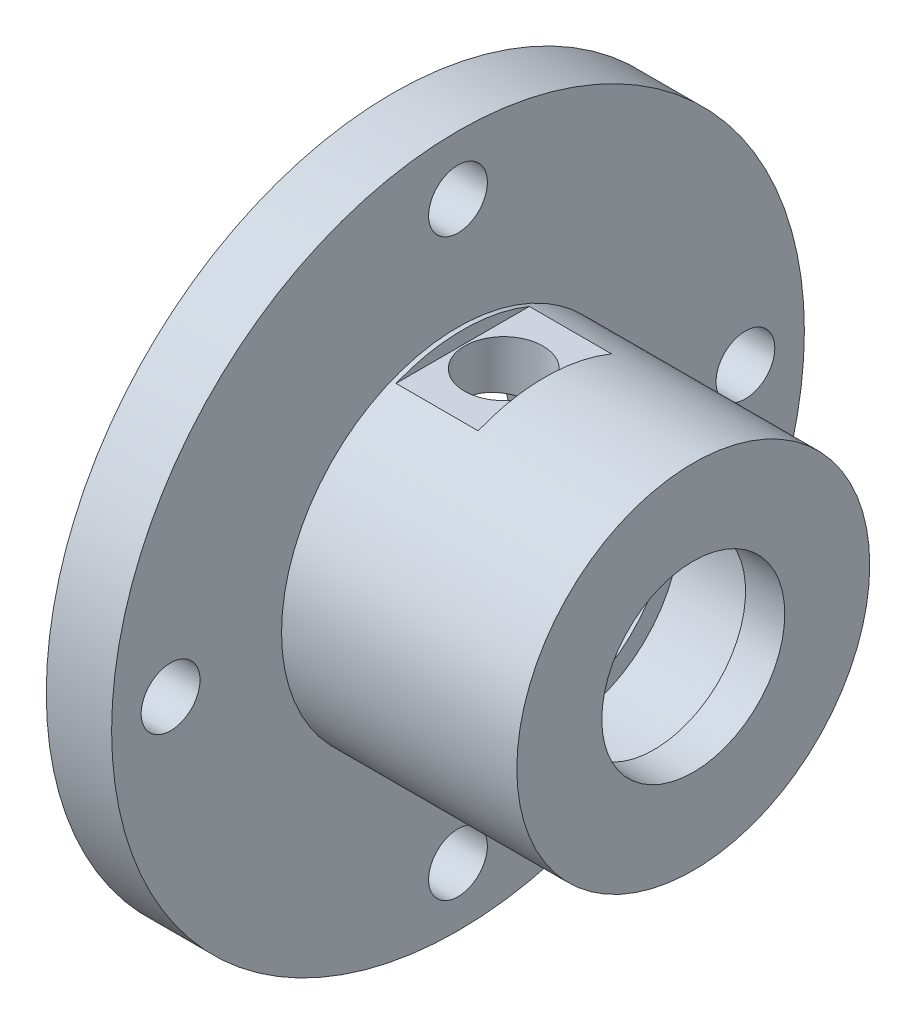
SolidWorks part; units mm, degrees
ref_plane "Front Plane" through (0, 0, 0) normal (0, 0, 1) x (1, 0, 0)
ref_plane "Top Plane" through (0, 0, 0) normal (0, 1, 0) x (1, 0, 0)
ref_plane "Right Plane" through (0, 0, 0) normal (1, 0, 0) x (0, 0, -1)
sketch "Sketch1" plane through (0, 0, 0) normal (1, 0, 0) x (0, 0, -1)
  circle A0 centre (0, 0) radius 26.5
  circle A2 centre (0, -21.9877) radius 2.25
  circle A3 centre (-21.9877, 0) radius 2.25
  circle A4 centre (0, 21.9877) radius 2.25
  circle A5 centre (21.9877, 0) radius 2.25
  point P3 (0, 0)
  point P14 (0, 0)
  dimension "D1" = 53
  dimension "D2" = 4
  dimension "D3" = 4.5
extrude "Boss-Extrude1" add sketch "Sketch1" along normal mid plane 23
sketch "Sketch2" plane through (11.5, 0, 0) normal (1, 0, 0) x (0, 0, -1)
  circle A0 centre (0, 0) radius 13.5
  circle A1 centre (0, 0) radius 26.5
  circle A2 centre (0, 0) radius 0.5
  circle M3 centre (0, 21.9877) radius 2.25
  circle M4 centre (0, -21.9877) radius 2.25
  circle M5 centre (0, 0) radius 26.5
  circle M6 centre (-21.9877, 0) radius 2.25
  circle M7 centre (21.9877, 0) radius 2.25
  dimension "D1" = 13
  dimension "D2" = 13
extrude "Cut-Extrude1" cut sketch "Sketch2" against normal blind 18 contours A0 M5 M4 M6 M7 M3 region at (11.5, 0, 25.7505)
sketch "Sketch3" plane through (-11.5, 0, 0) normal (-1, 0, 0) x (0, 0, 1)
  circle A0 centre (0, 0) radius 9
  dimension "D1" = 18
extrude "Cut-Extrude2" cut sketch "Sketch3" against normal blind 20
sketch "Sketch4" plane through (8.5, 0, 0) normal (-1, 0, 0) x (0, 0, 1)
  circle A0 centre (0, 0) radius 7
extrude "Cut-Extrude3" cut sketch "Sketch4" against normal blind 20
ref_plane "Plane1" through (1, 0, 0) normal (-1, 0, 0) x (0, 0, 1)
sketch "Sketch5" plane through (1, 0, 0) normal (-1, 0, 0) x (0, 0, 1)
  circle A0 centre (0, 0) radius 11
extrude "Cut-Extrude4" cut sketch "Sketch5" against normal mid plane 1
ref_axis "Axis1" through (26.7383, 0, 0) along (-1, 0, 0)
sketch "Sketch6" plane through (0, 0, 0) normal (0, 1, 0) x (1, 0, 0)
  line L0 (26.7383, 0) -> (-32.37, 0) construction
  line L1 (11.5, -13.5) -> (11.5, 13.5) construction
  circle A0 centre (-3, 0) radius 3
  dimension "D1" = 14.5
extrude "Cut-Extrude5" cut sketch "Sketch6" along normal blind 33
ref_plane "Plane3" through (0, 13.5, 0) normal (0, 1, 0) x (1, 0, 0)
sketch "Sketch8" plane through (0, 13.5, 0) normal (0, 1, 0) x (1, 0, 0)
  line L1 (0.1411, -6) -> (-6.1411, -6)
  line L2 (0.1411, -6) -> (0.1411, 6)
  line L3 (0.1411, 6) -> (-6.1411, 6)
  line L4 (-6.1411, -6) -> (-6.1411, 6)
  line L5 (0.1411, -6) -> (-6.1411, 6) construction
  line L6 (0.1411, 6) -> (-6.1411, -6) construction
  point P0 (-3, 0)
  dimension "D1" = 12
extrude "Cut-Extrude6" cut sketch "Sketch8" against normal blind 1
